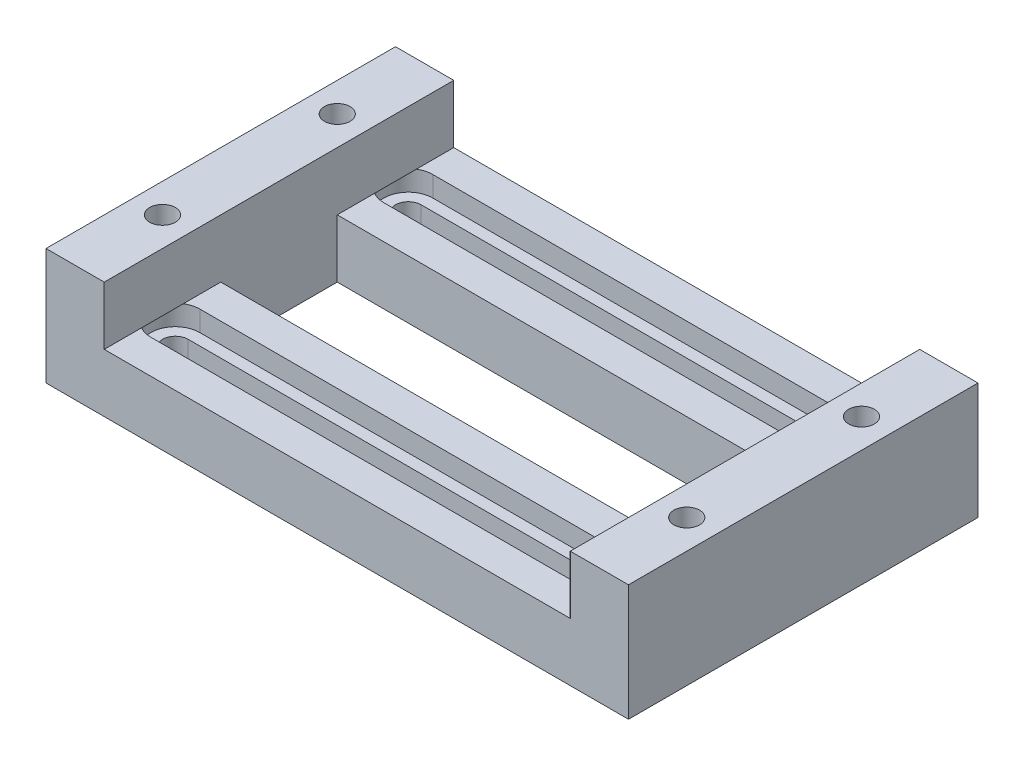
SolidWorks part; units mm, degrees
ref_plane "Front Plane" through (0, 0, 0) normal (0, 0, 1) x (1, 0, 0)
ref_plane "Top Plane" through (0, 0, 0) normal (0, 1, 0) x (1, 0, 0)
ref_plane "Right Plane" through (0, 0, 0) normal (1, 0, 0) x (0, 0, -1)
sketch "Sketch1" plane through (0, 0, 0) normal (0, 1, 0) x (1, 0, 0)
  line L0 (10, 40) -> (10, 20)
  line L1 (0, 0) -> (100, 0)
  line L2 (0, 0) -> (0, 60)
  line L3 (0, 60) -> (100, 60)
  line L4 (100, 0) -> (100, 60)
  line L5 (10, 20) -> (90, 20)
  line L6 (90, 20) -> (90, 40)
  line L7 (90, 40) -> (10, 40)
  line L8 (12.2, 10) -> (87.8, 10) construction
  line L9 (12.2, 12.2) -> (87.8, 12.2)
  line L10 (12.2, 7.8) -> (87.8, 7.8)
  line L11 (87.8, 50) -> (12.2, 50) construction
  line L12 (87.8, 47.8) -> (12.2, 47.8)
  line L13 (50, 0) -> (50, 20) construction
  line L14 (50, 40) -> (50, 60)
  line L15 (87.8, 52.2) -> (12.2, 52.2)
  circle A7 centre (5, 45) radius 2.2
  arc A22 (12.2, 12.2) -> (12.2, 7.8) centre (12.2, 10) ccw
  arc A23 (87.8, 7.8) -> (87.8, 12.2) centre (87.8, 10) ccw
  arc A24 (87.8, 47.8) -> (87.8, 52.2) centre (87.8, 50) ccw
  arc A25 (12.2, 52.2) -> (12.2, 47.8) centre (12.2, 50) ccw
  circle A29 centre (5, 15) radius 2.2
  circle A46 centre (95, 45) radius 2.2
  circle A47 centre (95, 15) radius 2.2
  point P13 (0, 0)
  point P14 (50, 50)
  point P17 (50, 10)
  point P22 (50, 50)
  point P33 (50, 10)
  point P34 (90, 10)
  point P35 (10, 10)
  point P36 (90, 50)
  point P37 (10, 50)
  dimension "D25" = 4.4
  dimension "D4" = 4.4
  dimension "D18" = 4.4
  dimension "D19" = 4.4
  dimension "D1" = 60
  dimension "D2" = 100
  dimension "D3" = 10
  dimension "D22" = 20
  dimension "D23" = 20
  dimension "D24" = 10
  dimension "D28" = 15
  dimension "D5" = 15
  dimension "D6" = 5
  dimension "D8" = 5
  dimension "D9" = 15
  dimension "D13" = 5
  dimension "D16" = 5
  dimension "D17" = 15
  dimension "D7" = 4.4
  dimension "D10" = 4.4
  dimension "D11" = 80
  dimension "D12" = 80
extrude "Boss-Extrude1" add sketch "Sketch1" along normal blind 10 contours L1 L4 L3 L2 A47 A46 A29 A7 L7 L6 L5 L0 region at (75, 0, -58.8338)
sketch "Sketch3" plane through (0, 10, 0) normal (0, 1, 0) x (1, 0, 0)
  line L8 (87.8, 14.2) -> (12.2, 14.2)
  line L9 (12.2, 5.8) -> (87.8, 5.8)
  line L10 (87.8, 54.2) -> (12.2, 54.2)
  line L11 (12.2, 45.8) -> (87.8, 45.8)
  arc A0 (12.2, 12.2) -> (12.2, 7.8) centre (12.2, 10) ccw construction
  arc A1 (12.2, 52.2) -> (12.2, 47.8) centre (12.2, 50) ccw construction
  arc A2 (87.8, 7.8) -> (87.8, 12.2) centre (87.8, 10) ccw construction
  arc A3 (87.8, 47.8) -> (87.8, 52.2) centre (87.8, 50) ccw construction
  arc A8 (12.2, 14.2) -> (12.2, 5.8) centre (12.2, 10) ccw
  arc A9 (87.8, 5.8) -> (87.8, 14.2) centre (87.8, 10) ccw
  arc A10 (87.8, 45.8) -> (87.8, 54.2) centre (87.8, 50) ccw
  arc A11 (12.2, 54.2) -> (12.2, 45.8) centre (12.2, 50) ccw
  point P12 (88.075, 13.6)
  point P13 (0, 0)
  point P19 (10.2221, 53.2866)
  point P24 (82.0373, 28.8937)
  point P25 (93.6969, 47.3734)
  dimension "D1" = 8.4
  dimension "D2" = 8.4
extrude "Cut-Slot insets" cut sketch "Sketch3" against normal blind 3.5
sketch "Sketch5" plane through (0, 10, 0) normal (0, 1, 0) x (1, 0, 0)
  line L2 (0, 60) -> (100, 60) construction
  line L3 (10, 60) -> (0, 60)
  line L4 (0, 60) -> (0, 0)
  line L5 (0, 0) -> (10, 0)
  line L6 (0, 0) -> (100, 0) construction
  line L9 (90, 0) -> (100, 0)
  line L10 (100, 0) -> (100, 60)
  line L11 (100, 60) -> (90, 60)
  line L20 (90, 60) -> (90, 0)
  line L21 (90, 20) -> (90, 40) construction
  line L22 (10, 0) -> (10, 60)
  line L23 (10, 40) -> (10, 20) construction
  circle A0 centre (95, 45) radius 2.2
  circle A3 centre (95, 15) radius 2.2
  circle A5 centre (5, 15) radius 2.2
  circle A8 centre (5, 45) radius 2.2
  circle A9 centre (5, 15) radius 2.2 construction
  circle A10 centre (5, 45) radius 2.2 construction
  circle A11 centre (95, 45) radius 2.2 construction
  circle A12 centre (95, 15) radius 2.2 construction
extrude "Boss-Extrude3" add sketch "Sketch5" along normal blind 10
sketch "Sketch6" plane through (0, 0, 0) normal (0, -1, 0) x (1, 0, 0)
  circle A0 centre (5, -45) radius 4.215
  circle A2 centre (5, -15) radius 4.215
  circle A3 centre (95, -15) radius 4.215
  circle A5 centre (95, -45) radius 4.215
  dimension "D1" = 8.43
  dimension "D3" = 8.43
  dimension "D4" = 8.43
  dimension "D6" = 8.43
extrude "Cut-Extrude1" cut sketch "Sketch6" against normal blind 2.5
chamfer "Chamfer1" distance 0.5 angle 45 8 edges at (50, 0, -52.2) (90, 0, -50) (10, 0, -50) (50, 0, -47.8) (50, 0, -7.8) (10, 0, -10) (90, 0, -10) (50, 0, -12.2)
chamfer "Chamfer2" distance 1 angle 45 4 edges at (95, 2.5, -19.215) (95, 2.5, -49.215) (5, 2.5, -49.215) (5, 2.5, -19.215)
equation "\"boltdiameter\"=4.4"
equation "\"D25@Sketch1\"=\"boltdiameter\""
equation "\"D4@Sketch1\"=\"boltdiameter\""
equation "\"D18@Sketch1\"=\"boltdiameter\""
equation "\"D19@Sketch1\"=\"boltdiameter\""
equation "\"boltfacediameter\"=7"
equation "\"insetNutFlat\"=8.4"
equation "\"D1@Sketch3\"=\"insetNutFlat\""
equation "\"D2@Sketch3\"=\"insetNutFlat\""
equation "\"screwInset\"=8.43"
equation "\"D1@Sketch6\"=\"screwInset\""
equation "\"D3@Sketch6\"=\"screwInset\""
equation "\"D4@Sketch6\"=\"screwInset\""
equation "\"D6@Sketch6\"=\"screwInset\""
equation "\"D7@Sketch1\"=\"boltdiameter\""
equation "\"D10@Sketch1\"=\"boltdiameter\""
equation "\"slotLength\"=80"
equation "\"D11@Sketch1\"=\"slotLength\""
equation "\"D12@Sketch1\"=\"slotLength\""
